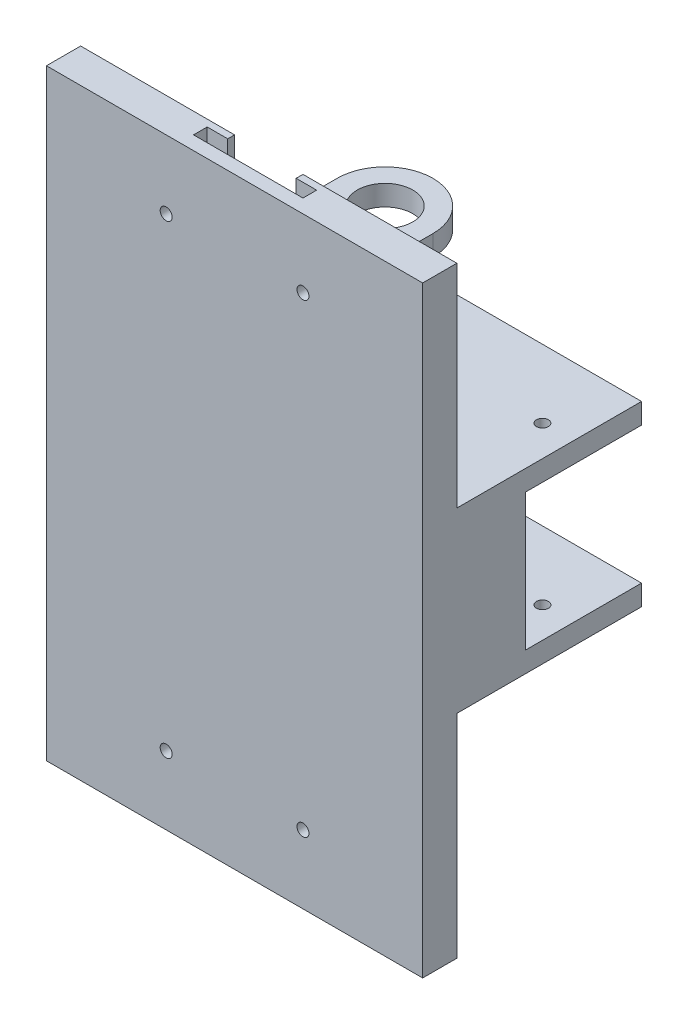
SolidWorks part; units mm, degrees
ref_plane "Front Plane" through (0, 0, 0) normal (0, 0, 1) x (1, 0, 0)
ref_plane "Top Plane" through (0, 0, 0) normal (0, 1, 0) x (1, 0, 0)
ref_plane "Right Plane" through (0, 0, 0) normal (1, 0, 0) x (0, 0, -1)
sketch "Sketch1" plane through (0, 0, 0) normal (0, 1, 0) x (1, 0, 0)
  line L0 (23.0125, 0) -> (-23.0125, 0) construction
  line L1 (-27.5, -17) -> (-5, -17)
  line L2 (-27.5, 10) -> (27.5, 10)
  line L3 (-27.5, 10) -> (-27.5, -22)
  line L4 (-27.5, -22) -> (27.5, -22)
  line L5 (27.5, 10) -> (27.5, -22)
  line L6 (-5, -17) -> (-5, -18)
  line L7 (-8, -20) -> (8, -20)
  line L8 (-5, -18) -> (-8, -18)
  line L9 (5, -17) -> (27.5, -17)
  line L10 (-5, -17) -> (5, -17)
  line L11 (-7, 0) -> (-7, -17)
  line L12 (7, 0) -> (7, -17)
  line L13 (-8, -18) -> (-8, -20)
  line L14 (5, -17) -> (5, -18)
  line L15 (5, -18) -> (8, -18)
  line L16 (8, -18) -> (8, -20)
  circle A0 centre (-23.0125, 0) radius 0.875
  circle A1 centre (23.0125, 0) radius 0.875
  circle A2 centre (0, 0) radius 6.5
  circle A3 centre (0, 0) radius 4.05
  arc A4 (7, 0) -> (-7, 0) centre (0, 0) ccw
  point P4 (0, 0)
  point P13 (0, 10)
  point P16 (0, -20)
  dimension "D1" = 1.75
  dimension "D3" = 13
  dimension "D11" = 8.1
  dimension "D12" = 7
  dimension "D2" = 46.025
  dimension "D4" = 3
  dimension "D5" = 2
  dimension "D6" = 10
  dimension "D7" = 55
  dimension "D8" = 10
  dimension "D9" = 17
  dimension "D10" = 5
  dimension "D13" = 16
extrude "Boss-Extrude1" add sketch "Sketch1" along normal blind 3 contours A1 L12 L9 L5 L2 L3 L1 L11 A0 A4 | L9 L7 L1 L3 L4 L5 | L10 L7 | L12 L0 A2 L11 L1 L10 L9 | L0 A4 A2 region at (0, 0, 10.72) region at (0, 0, -7.6127) region at (6.75, 0, -0.1565) region at (17.25, 0, 17.5523) region at (0, 0, 18.6429)
extrude "Boss-Extrude2" add sketch "Sketch1<4>" along normal blind 13 from surface contours L9 L7 L1 L3 L4 L5 | L10 L7 region at (-17.25, 0, 17.5523) region at (0, 0, 18.6429) starting at face at (0, 3, 6.5)
sketch "Sketch1<4>" plane through (0, 0, 0) normal (0, 1, 0) x (1, 0, 0) same geometry as "Sketch1"
extrude "Boss-Extrude3" add sketch "Sketch1<5>" along normal blind 3 from surface contours L12 L0 A2 L11 L1 L10 L9 | A2 L0 A3 | L0 A2 A3 | L0 A4 A2 | L9 L7 L1 L3 L4 L5 | L10 L7 region at (0, 0, 10.72) region at (6.75, 0, -0.1565) region at (0, 0, 6.3547) region at (5.275, 0, -0.1453) region at (17.25, 0, 17.5523) region at (0, 0, 18.6429) starting at face at (0, 16, 19.5)
sketch "Sketch1<5>" plane through (0, 0, 0) normal (0, 1, 0) x (1, 0, 0) same geometry as "Sketch1"
extrude "Boss-Extrude4" add sketch "Sketch1<6>" along normal blind 15 from surface contours L9 L7 L1 L3 L4 L5 region at (-17.25, 0, 17.5523) starting at face at (0, 19, 13.125)
sketch "Sketch1<6>" plane through (0, 0, 0) normal (0, 1, 0) x (1, 0, 0) same geometry as "Sketch1"
extrude "Boss-Extrude5" add sketch "Sketch1<7>" against normal blind 10 contours L9 L7 L1 L3 L4 L5 | L10 L7 region at (-17.25, 0, 17.5523) region at (0, 0, 18.6429)
sketch "Sketch1<7>" plane through (0, 0, 0) normal (0, 1, 0) x (1, 0, 0) same geometry as "Sketch1"
sketch "Sketch2" plane through (0, 0, 17) normal (0, 0, -1) x (-1, 0, 0)
  line L0 (-10, 24) -> (10, 24) construction
  line L1 (7, 19) -> (-7, 19) construction
  circle A0 centre (-10, 24) radius 0.875
  circle A1 centre (10, 24) radius 0.875
  point P2 (0, 24)
  dimension "D1" = 1.75
  dimension "D2" = 20
  dimension "D3" = 5
extrude "Cut-Extrude1" cut sketch "Sketch2" against normal through all
chamfer "Chamfer1" distance 5 angle 45 2 edges at (7, 17.5, 17) (-7, 17.5, 17)
ref_plane "Plane1" through (0, -10, 0) normal (0, -1, 0) x (-1, 0, 0)
mirror "Mirror4" about plane through (0, -10, 0) normal (0, -1, 0) of "Chamfer1", "Cut-Extrude1", "Boss-Extrude5", "Boss-Extrude4", "Boss-Extrude3", "Boss-Extrude2", "Boss-Extrude1"
sketch "Sketch3" plane through (0, -23, 0) normal (0, -1, 0) x (1, 0, 0)
  line L0 (-27.5, -10) -> (-27.5, 17) construction
  line L1 (-27.5, 7) -> (-22.5, 7)
  line L2 (-27.5, 7) -> (-27.5, 17)
  line L3 (-27.5, 17) -> (-22.5, 17)
  line L4 (-22.5, 7) -> (-22.5, 17)
  line L5 (5, 17) -> (27.5, 17) construction
  line L6 (22.5, 17) -> (27.5, 17)
  line L7 (22.5, 17) -> (22.5, 7)
  line L8 (22.5, 7) -> (27.5, 7)
  line L9 (27.5, 17) -> (27.5, 7)
  line L10 (27.5, -10) -> (27.5, 17) construction
  line L11 (-27.5, 17) -> (-5, 17) construction
  dimension "D1" = 10
  dimension "D2" = 5
extrude "Boss-Extrude6" add sketch "Sketch3" against normal up to surface (23 mm away) up to face at (23.0125, 0, 0.875)
